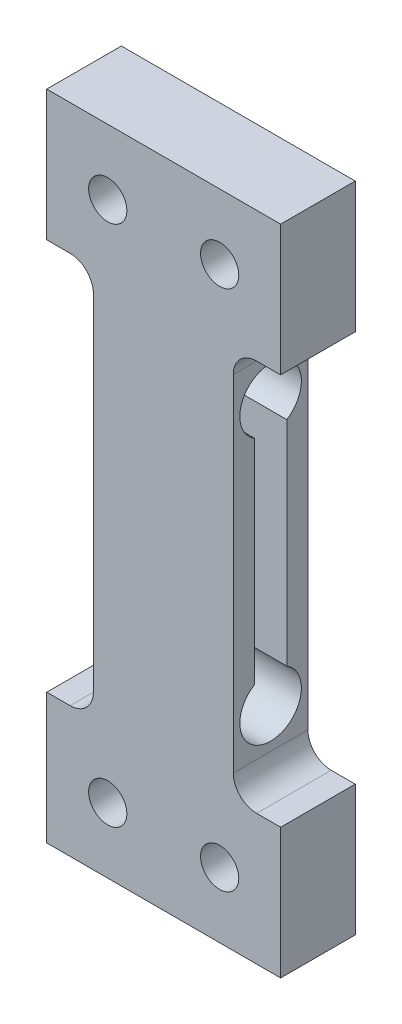
SolidWorks part; units mm, degrees
ref_plane "Front Plane" through (0, 0, 0) normal (0, 0, 1) x (1, 0, 0)
ref_plane "Top Plane" through (0, 0, 0) normal (0, 1, 0) x (1, 0, 0)
ref_plane "Right Plane" through (0, 0, 0) normal (1, 0, 0) x (0, 0, -1)
ref_plane "Plane1" through (0, 0, 4) normal (0, 0, 1) x (1, 0, 0)
sketch "Sketch1" plane through (0, 0, 4) normal (0, 0, 1) x (1, 0, 0)
  line L0 (-10, 35) -> (-10, 0)
  line L1 (-10, 0) -> (2.5384, 0)
  line L2 (2.5384, 0) -> (2.5384, 35)
  line L3 (2.5384, 35) -> (-10, 35)
extrude "Boss-Extrude1" add sketch "Sketch1" against normal blind 4
sketch "Sketch2" plane through (0, 0, 0) normal (0, 0, -1) x (-1, 0, 0)
  line L0 (10, 28) -> (7.5, 28)
  line L1 (7.5, 28) -> (7.5, 7)
  line L2 (7.5, 7) -> (10, 7)
  line L3 (10, 7) -> (10, 28)
extrude "Cut-Extrude1" cut sketch "Sketch2" against normal through all
sketch "Sketch3" plane through (0, 0, 0) normal (0, 0, -1) x (-1, 0, 0)
  line L0 (-2.5384, 7) -> (0, 7)
  line L1 (0, 7) -> (0, 28)
  line L2 (0, 28) -> (-2.5384, 28)
  line L3 (-2.5384, 28) -> (-2.5384, 7)
extrude "Cut-Extrude2" cut sketch "Sketch3" against normal through all
sketch "Sketch4" plane through (-7.5, 0, 0) normal (-1, 0, 0) x (0, 0, 1)
  line L0 (2.8559, 11.7856) -> (2.8559, 23.2144)
  line L1 (1.1318, 23.2219) -> (1.1318, 11.7781)
  arc A0 (1.1318, 11.7781) -> (2.8559, 11.7856) centre (2, 10.375) cw
  arc A1 (2.8559, 23.2144) -> (1.1318, 23.2219) centre (2, 24.625) cw
extrude "Cut-Extrude3" cut sketch "Sketch4" against normal through all
ref_plane "Plane2" through (0, 0, 2) normal (0, 0, -1) x (-1, 0, 0)
sketch "Sketch5" plane through (0, 0, 2) normal (0, 0, -1) x (-1, 0, 0)
  line L0 (0, 26.275) -> (0, 24.625)
  line L1 (0, 24.625) -> (7.5, 24.625)
  line L2 (7.5, 24.625) -> (7.5, 26.275)
  line L3 (7.5, 26.275) -> (0, 26.275)
  line L4 (0, 24.625) -> (7.5, 24.625) construction
revolve "Cut-Revolve1" cut sketch "Sketch5" angle 360 about L4 reverse direction yes
sketch "Sketch6" plane through (0, 0, 2) normal (0, 0, -1) x (-1, 0, 0)
  line L0 (0, 12.025) -> (0, 10.375)
  line L1 (0, 10.375) -> (7.5, 10.375)
  line L2 (7.5, 10.375) -> (7.5, 12.025)
  line L3 (7.5, 12.025) -> (0, 12.025)
  line L4 (0, 10.375) -> (7.5, 10.375) construction
revolve "Cut-Revolve2" cut sketch "Sketch6" angle 360 about L4 reverse direction yes
hole_wizard "M2.5x0.45 Tapped Hole1" positions "Sketch8" profile "Sketch7" tap size "M2.5x0.45" standard "Ansi Metric" end condition through all
sketch "Sketch8" plane through (0, 0, 4) normal (0, 0, 1) x (1, 0, 0)
  point P0 (-0.7308, 3.5)
  point P1 (-6.7308, 3.5)
  point P2 (-0.7308, 31.5)
  point P3 (-6.7308, 31.5)
sketch "Sketch7" plane through (-0.7308, 3.5, 4) normal (1, 0, 0) x (0, -1, 0)
  line L0 (0, 0) -> (0, 4)
  line L1 (0, 4) -> (1.025, 4)
  line L2 (1.025, 4) -> (1.025, 0)
  line L5 (1.025, 0) -> (0, 0)
  line L11 (0, -6.35) -> (0, 107.95) construction
  dimension "Thread Major Dia." = 2.05
  dimension "Thru Tap Drill Depth" = 4
fillet "Fillet1" radius 1.25 4 edges at (-7.5, 28, 2) (-7.5, 7, 2) (0, 28, 2) (0, 7, 2) tangent propagation no
